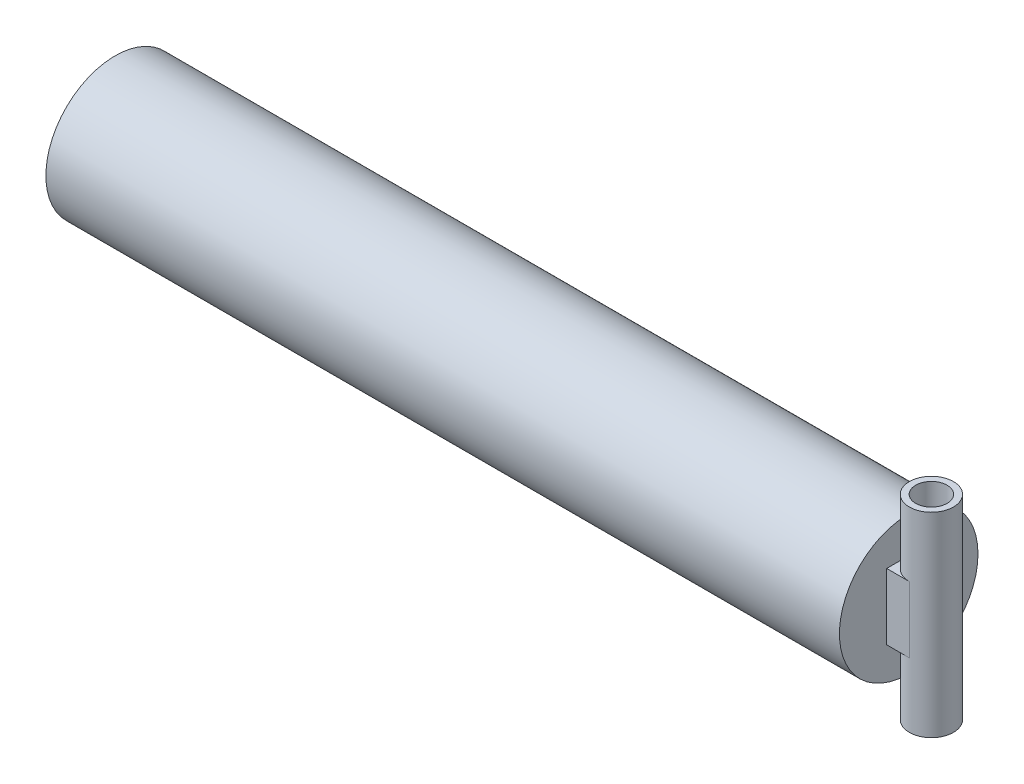
SolidWorks part; units mm, degrees
material "Plain Carbon Steel"
ref_plane "Front Plane" through (0, 0, 0) normal (0, 0, 1) x (1, 0, 0)
ref_plane "Top Plane" through (0, 0, 0) normal (0, 1, 0) x (1, 0, 0)
ref_plane "Right Plane" through (0, 0, 0) normal (1, 0, 0) x (0, 0, -1)
sketch "cilindar_Sketch2" plane through (0, 0, 0) normal (0, 1, 0) x (1, 0, 0)
  circle A0 centre (666, 0) radius 35
  circle A1 centre (666, 0) radius 25
  dimension "D2" = 70
  dimension "D3" = 50
  dimension "D1" = 666
sketch "cilindar_Sketch1" plane through (0, 0, 0) normal (0, 1, 0) x (1, 0, 0)
  line L0 (-630, 0) -> (630, 0)
  line L1 (630, 0) -> (630, 100)
  line L2 (630, 100) -> (600, 100)
  line L3 (600, 100) -> (600, 110)
  line L4 (600, 110) -> (-600, 110)
  line L6 (-600, 110) -> (-600, 100)
  line L7 (-600, 100) -> (-630, 100)
  line L8 (-630, 100) -> (-630, 0)
  dimension "D1" = 110
  dimension "D3" = 30
  dimension "D2" = 1200
  dimension "D4" = 100
revolve "cilindar_Revolve1" add sketch "cilindar_Sketch1" angle 360 about L0 region at (0, 0, -54.7826)
shell "cilindar_Shell1" thickness 10 removed face at (-630, 0, 100)
sketch "cilindar_Sketch3" plane through (0, 0, 0) normal (0, 1, 0) x (1, 0, 0)
  line L0 (-600, 110) -> (-600, -110) construction
  line L1 (-600, 110) -> (-600, -110) construction
  line L2 (-630, 100) -> (-630, -100) construction
  line L3 (-630, 100) -> (-630, -100) construction
  line L4 (-630, 100) -> (-600, 100)
  line L5 (-600, 100) -> (-600, 110)
  line L6 (-600, 110) -> (-630, 110)
  line L7 (-630, 110) -> (-630, 100)
ref_axis "cilindar_Axis1" through (590, 0, 0) along (-1, 0, 0)
revolve "cilindar_Revolve2" add sketch "cilindar_Sketch3" angle 360 about axis through (590, 0, 0) along (-1, 0, 0)
mirror "cilindar_Mirror2" about plane through (0, 0, 0) normal (1, 0, 0) of "cilindar_Revolve2"
extrude "cilindar_Boss-Extrude1" add sketch "cilindar_Sketch2" along normal blind 155 and the other way blind 155 separate body
sketch "cilindar_Sketch6" plane through (630, 0, 0) normal (1, 0, 0) x (0, 0, -1)
  line L0 (-35, 155) -> (-35, -155) construction
  line L1 (35, -155) -> (35, 155) construction
  line L2 (-35, 155) -> (-35, -155) construction
  line L3 (35, -155) -> (35, 155) construction
  line L4 (35, 52.5) -> (35, -52.5)
  line L5 (-35, 52.5) -> (-35, -52.5) construction
  line L6 (35, 52.5) -> (-35, 52.5)
  line L7 (-35, -52.5) -> (35, 52.5) construction
  line L8 (35, -52.5) -> (-35, -52.5)
  line L9 (-35, 52.5) -> (-35, -52.5)
  dimension "D1" = 105
extrude "cilindar_Boss-Extrude7" add sketch "cilindar_Sketch6" along normal up to next
sketch "cilindar_Sketch7" plane through (-630, 0, 0) normal (-1, 0, 0) x (0, 0, 1)
  circle A2 centre (0, 0) radius 25
  circle A3 centre (0, 0) radius 90 construction
  circle A4 centre (0, 0) radius 90
  dimension "D1" = 50
extrude "cilindar_Boss-Extrude8" add sketch "cilindar_Sketch7" against normal blind 10
equation "\"sirina_klipa\"= 200"
equation "\"debljina_klipa\"= 20"
equation "\"sirina_klipnjace\"= \"sirina_klipa\" / 4"
equation "\"duljina_klipnjace\"= 1200"
equation "\"r2_v\"= 70"
equation "\"r2_u\"= 50"
equation "\"r1_v\"= 70"
equation "\"r1_u\"= 50"
equation "\"l2\"= 310"
equation "\"l1\"= 310"
equation "\"sirina_cilindra\"= \"sirina_klipa\" + 2 * \"debljina_stijenke\""
equation "\"duljina_komore\"= 30"
equation "\"debljina_stijenke\"= 10"
equation "\"D3@cilindar_Sketch1\"= \"duljina_komore\""
equation "\"D4@cilindar_Sketch1\"=\"sirina_klipa\"/2"
equation "\"D1@cilindar_Sketch1\"=\"sirina_cilindra\"/2"
equation "\"D2@cilindar_Sketch1\"= \"duljina_cilindra\""
equation "\"D1@cilindar_Shell1\"=\"debljina_stijenke\""
equation "\"duljina_cilindra\"= \"duljina_klipnjace\" + \"debljina_klipa\" + \"debljina_stijenke\" - \"duljina_komore\""
equation "\"D1@cilindar_Sketch2\"=\"duljina_cilindra\"/2 + \"duljina_komore\" + \"r1_v\"/2 + 1"
equation "\"D2@cilindar_Sketch2\"=\"r1_v\""
equation "\"D3@cilindar_Sketch2\"=\"r1_u\""
equation "\"D1@cilindar_Sketch7\" = \"sirina_klipnjace\""
equation "\"D2@cilindar_Boss-Extrude1\"=\"l1\"/2"
equation "\"D1@cilindar_Boss-Extrude1\"=\"l1\"/2"
